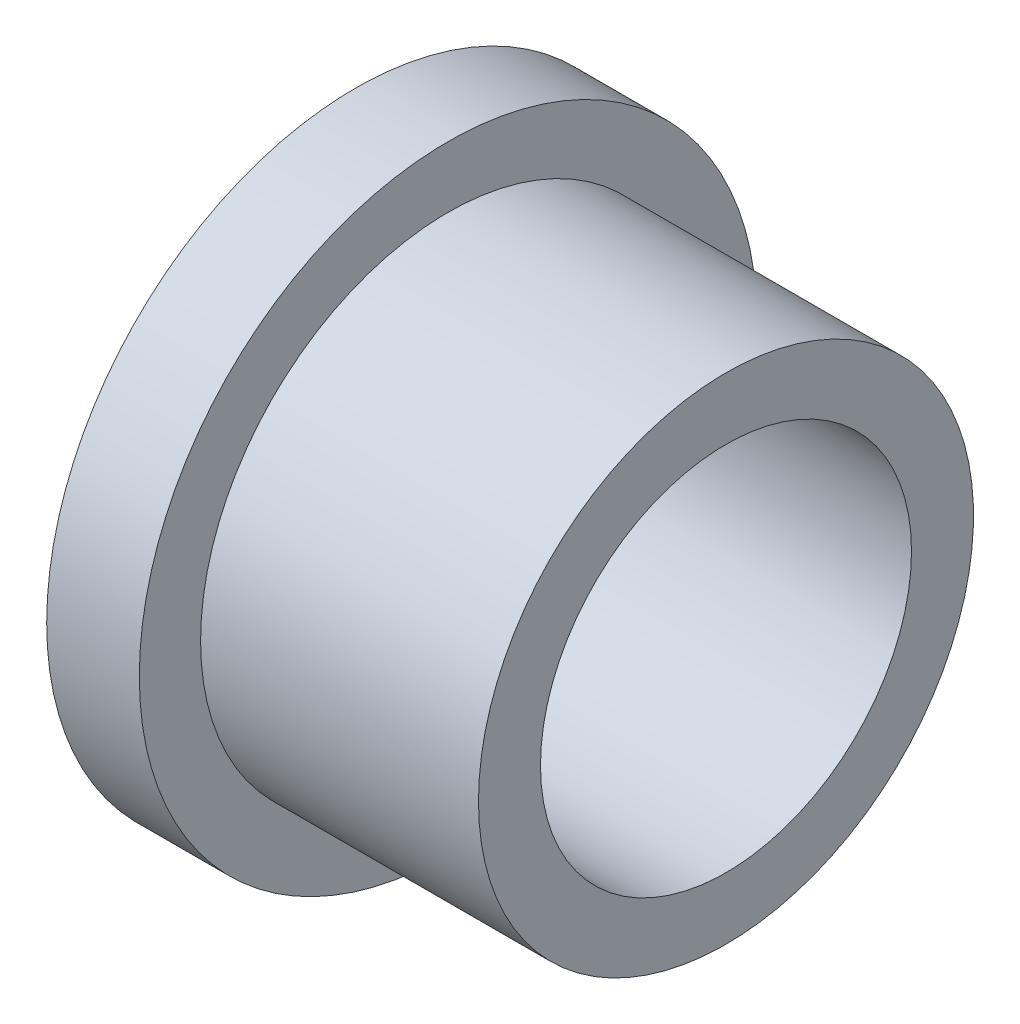
SolidWorks part; units mm, degrees
material "Ductile Iron"
ref_plane "X-Y Datum" through (0, 0, 0) normal (0, 0, 1) x (1, 0, 0)
ref_plane "X-Z Datum" through (0, 0, 0) normal (0, 1, 0) x (1, 0, 0)
ref_plane "Y-Z Datum" through (0, 0, 0) normal (1, 0, 0) x (0, 0, -1)
sketch "Sketch1" plane through (0, 0, 0) normal (1, 0, 0) x (0, 0, -1)
  circle A0 centre (0, 0) radius 15.875
  circle A1 centre (0, 0) radius 12.7254
  circle A2 centre (0, 0) radius 9.5377
  dimension "D1" = 31.75
  dimension "D2" = 25.4508
  dimension "D3" = 19.0754
extrude "Boss-Extrude1" add sketch "Sketch1" along normal blind 4.7625 contours A0 | A2
extrude "Boss-Extrude2" add sketch "Sketch1<3>" along normal blind 19.05 contours A1 | A2
sketch "Sketch1<3>" plane through (0, 0, 0) normal (1, 0, 0) x (0, 0, -1) same geometry as "Sketch1"
